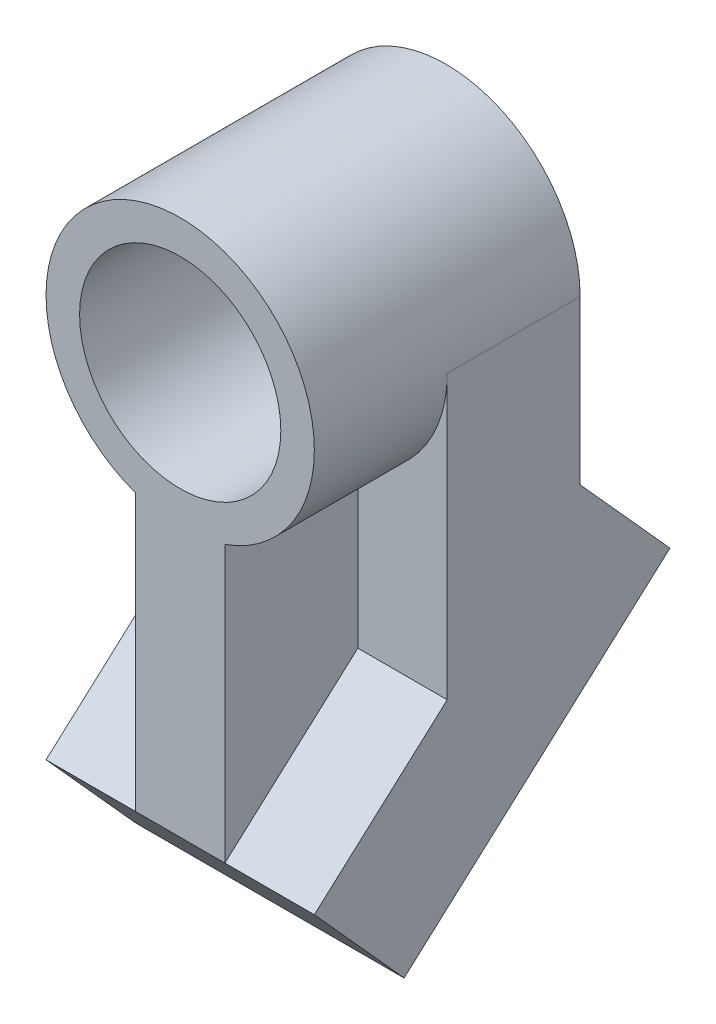
SolidWorks part; units mm, degrees
ref_plane "정면" through (0, 0, 0) normal (0, 0, 1) x (1, 0, 0)
ref_plane "윗면" through (0, 0, 0) normal (0, 1, 0) x (1, 0, 0)
ref_plane "우측면" through (0, 0, 0) normal (1, 0, 0) x (0, 0, -1)
sketch "스케치1" plane through (0, 0, 0) normal (0, 0, 1) x (1, 0, 0)
  line L0 (-5, -45) -> (5, -45)
  line L1 (5, -45) -> (5, -14.1421)
  line L2 (-5, -45) -> (-5, -14.1421)
  line L3 (0, 0) -> (0, -45) construction
  circle A0 centre (0, 0) radius 15
  circle A1 centre (0, 0) radius 11.25
  point P8 (0, -46.0109)
  dimension "D1" = 30
  dimension "D2" = 22.5
  dimension "D3" = 10
  dimension "D4" = 45
extrude "보스-돌출1" add sketch "스케치1" along normal blind 14.86 contours A1 A0 | L3 A0 L2 L0 | A0 L3 L0 L1 region at (-2.5117, -29.8576, 0) region at (2.5117, -29.8576, 0) region at (-8.4153, 11.901, 0)
sketch "스케치2" plane through (0, 0, 0) normal (0, 0, -1) x (-1, 0, 0)
  line L0 (-15, 0) -> (-15, -32)
  line L1 (-15, -32) -> (15, -32)
  line L2 (15, -32) -> (15, 0)
  circle A0 centre (0, 0) radius 11.25
  circle A1 centre (0, 0) radius 15
  line M2 (-5, -45) -> (5, -45)
  line M3 (5, -45) -> (5, -14.1421)
  arc M4 (5, -14.1421) -> (-5, -14.1421) centre (0, 0) ccw
  line M5 (-5, -14.1421) -> (-5, -45)
  circle M6 centre (0, 0) radius 11.25
  dimension "D1" = 32
extrude "보스-돌출2" add sketch "스케치2" along normal blind 14.86 contours L0 L1 M5 M4 | A1 M5 M2 M3 | L1 L2 M4 M3 | A1 M4 M6 region at (10.4079, -20.9186, 0) region at (0, 14.5757, 0) region at (-10.4079, -20.9186, 0) region at (0, -23.3568, 0)
sketch "스케치4" plane through (-5, 0, 0) normal (-1, 0, 0) x (0, 0, 1)
  line L1 (14.86, -45) -> (-14.8658, -18.2348)
  line L2 (-14.8658, -18.2348) -> (-24.9028, -29.3819)
  line L3 (-24.9028, -29.3819) -> (4.823, -56.1472)
  line L4 (4.823, -56.1472) -> (14.86, -45)
  line L5 (14.86, -45) -> (14.86, -14.1421) construction
  dimension "D1" = 48
  dimension "D2" = 40
  dimension "D3" = 15
extrude "보스-돌출4" add sketch "스케치4" along normal blind 10
extrude "보스-돌출5" add sketch "스케치4<2>" against normal blind 20
sketch "스케치4<2>" plane through (-5, 0, 0) normal (-1, 0, 0) x (0, 0, 1) same geometry as "스케치4"
hole_wizard "M3.5 나사 구멍1" positions "스케치9" profile "스케치10" tap size "M3.5" standard "ISO"
sketch "스케치9" plane through (0, -28.6098, -25.7603) normal (0, -0.7431, -0.6691) x (-1, 0, 0)
  line L1 (15, -41.154) -> (-15, -41.154) construction
  line L2 (15, -1.154) -> (15, -41.154) construction
  point P0 (10, -31.154)
  point P10 (-10, -31.154)
  point P11 (-10, -11.154)
  point P12 (10, -11.154)
  dimension "D3" = 10
  dimension "D4" = 5
  dimension "D1" = 2
  dimension "D2" = 2
sketch "스케치10" plane through (-10, -49.4559, -2.6084) normal (1, 0, 0) x (0, 0.6691, -0.7431)
  line L0 (0, 0) -> (0, 10.8712)
  line L1 (0, 10.8712) -> (1.45, 10)
  line L2 (1.45, 10) -> (1.45, 0)
  line L5 (1.45, 0) -> (0, 0)
  line L10 (0, 10.8712) -> (-1.45, 10) construction
  line L11 (0, -6.35) -> (0, 107.95) construction
  dimension "탭 드릴 지름" = 2.9
  dimension "탭 드릴 깊이" = 10
  dimension "드릴 각도" = 118
cosmetic thread "구멍 나사산1" parameters "D1"=7, "D2"=3.5
cosmetic thread "구멍 나사산2" parameters "D1"=7, "D2"=3.5
cosmetic thread "구멍 나사산3" parameters "D1"=7, "D2"=3.5
cosmetic thread "구멍 나사산4" parameters "D1"=7, "D2"=3.5
